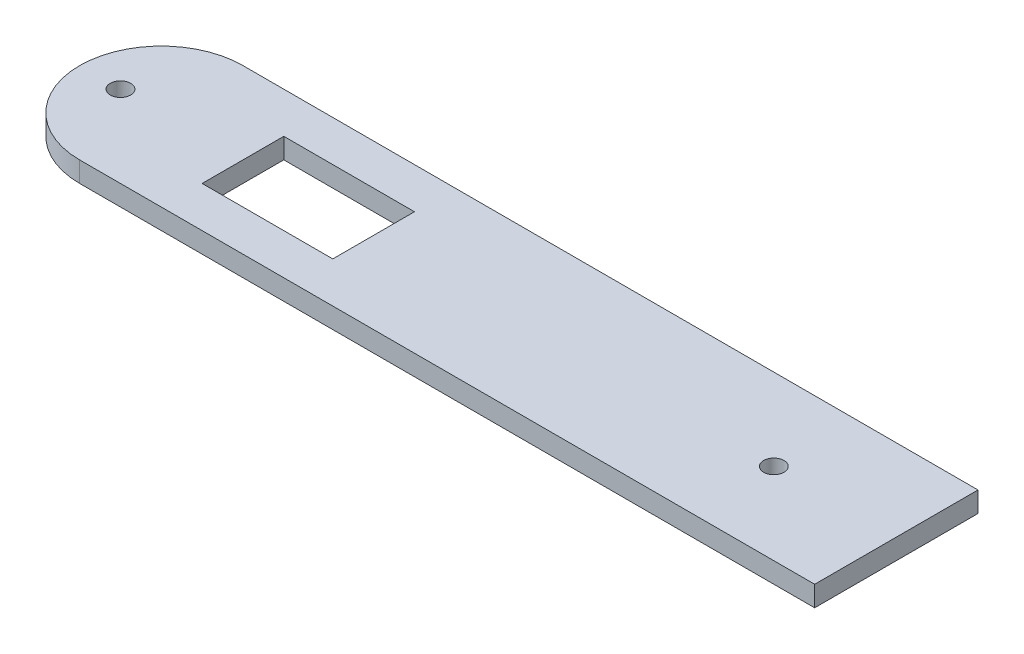
SolidWorks part; units mm, degrees
ref_plane "Front Plane" through (0, 0, 0) normal (0, 0, 1) x (1, 0, 0)
ref_plane "Top Plane" through (0, 0, 0) normal (0, 1, 0) x (1, 0, 0)
ref_plane "Right Plane" through (0, 0, 0) normal (1, 0, 0) x (0, 0, -1)
sketch "Sketch1" plane through (0, 0, 0) normal (0, 1, 0) x (1, 0, 0)
  line L1 (-34.1213, -15.4692) -> (219.8787, -15.4692)
  line L2 (-34.1213, -15.4692) -> (-34.1213, 35.3308)
  line L3 (-34.1213, 35.3308) -> (219.8787, 35.3308)
  line L4 (219.8787, -15.4692) -> (219.8787, 35.3308)
  dimension "D1" = 50.8
  dimension "D2" = 254
extrude "Boss-Extrude1" add sketch "Sketch1" along normal blind 6.35
hole_wizard "1/4 (0.25) Diameter Hole1" positions "Sketch3" profile "Sketch2" hole size "1/4" standard "ANSI Inch" end condition through all
sketch "Sketch3" plane through (0, 6.35, 0) normal (0, 1, 0) x (1, 0, 0)
  line L0 (-34.1213, 35.3308) -> (-34.1213, -15.4692) construction
  line L1 (219.8787, 35.3308) -> (-34.1213, 35.3308) construction
  point P0 (-21.4213, 9.9308)
  point P7 (181.7787, 9.9308)
  dimension "D1" = 12.7
  dimension "D2" = 25.4
  dimension "D3" = 203.2
sketch "Sketch2" plane through (-21.4213, 6.35, -9.9308) normal (1, 0, 0) x (0, 0, 1)
  line L0 (0, 0) -> (0, 6.35)
  line L1 (0, 6.35) -> (3.175, 6.35)
  line L2 (3.175, 6.35) -> (3.175, 0)
  line L5 (3.175, 0) -> (0, 0)
  line L11 (0, -6.35) -> (0, 107.95) construction
  dimension "Thru Hole Dia." = 6.35
  dimension "Thru Hole Depth" = 6.35
fillet "Fillet1" radius 25.4 2 edges at (-34.1213, 3.175, 15.4692) (-34.1213, 3.175, -35.3308)
sketch "Sketch4" plane through (0, 6.35, 0) normal (0, 1, 0) x (1, 0, 0)
  line L0 (219.8787, 35.3308) -> (-8.7213, 35.3308) construction
  line L1 (16.6787, 22.6308) -> (57.3187, 22.6308)
  line L2 (16.6787, 22.6308) -> (16.6787, -2.7692)
  line L3 (16.6787, -2.7692) -> (57.3187, -2.7692)
  line L4 (57.3187, 22.6308) -> (57.3187, -2.7692)
  circle A0 centre (-21.4213, 9.9308) radius 3.175 construction
  dimension "D4" = 38.1
  dimension "D1" = 25.4
  dimension "D2" = 40.64
  dimension "D3" = 12.7
extrude "Cut-Extrude1" cut sketch "Sketch4" against normal blind 25.4
